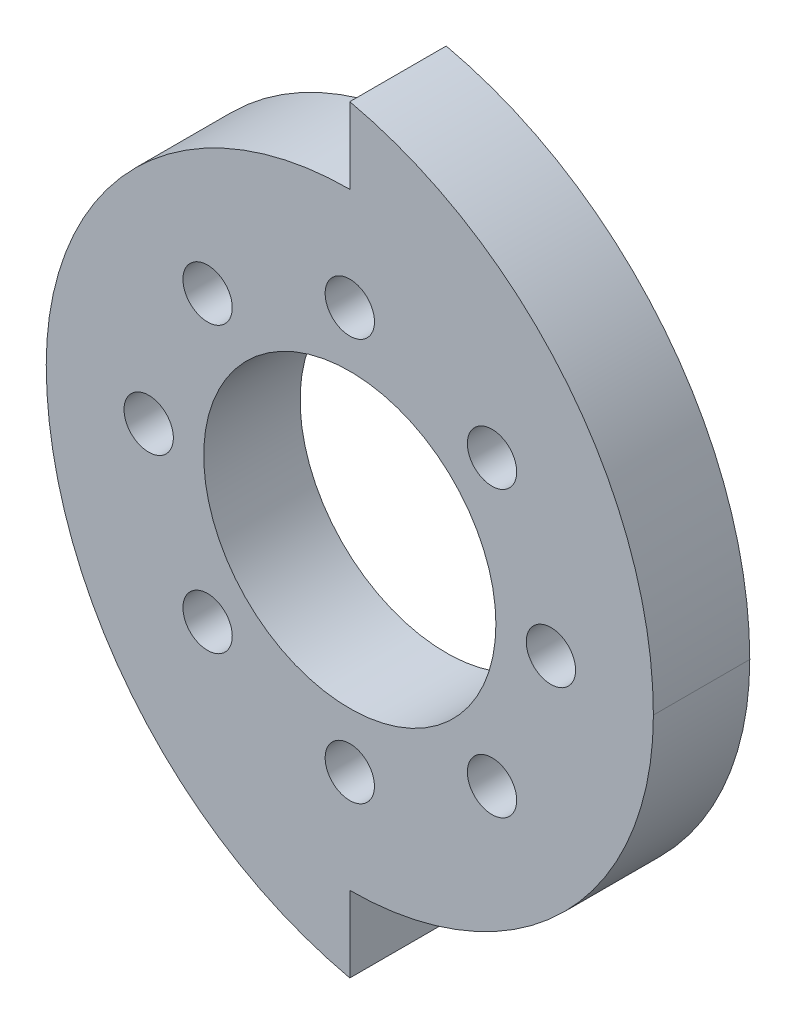
SolidWorks part; units mm, degrees
material "AISI 316 Stainless Steel Sheet (SS)"
ref_plane "Front Plane" through (0, 0, 0) normal (0, 0, 1) x (1, 0, 0)
ref_plane "Top Plane" through (0, 0, 0) normal (0, 1, 0) x (1, 0, 0)
ref_plane "Right Plane" through (0, 0, 0) normal (1, 0, 0) x (0, 0, -1)
sketch "Sketch3" plane through (0, 0, 0) normal (0, 0, 1) x (1, 0, 0)
  line L5 (0, 20) -> (0, 25)
  line L12 (0, -20) -> (0, -25)
  arc A9 (0, 25) -> (-20, 0) centre (5.625, 0) ccw construction
  arc A11 (0, -25) -> (20, 0) centre (-5.625, 0) ccw construction
  arc A14 (0, 25) -> (20, 0) centre (-5.625, 0) cw
  arc A15 (0, -25) -> (-20, 0) centre (5.625, 0) cw
  arc A16 (0, 20) -> (-20, 0) centre (0, 0) ccw
  arc A17 (20, 0) -> (0, -20) centre (0, 0) cw
  dimension "D2" = 5
  dimension "D1" = 40
extrude "Boss-Extrude1" add sketch "Sketch3" along normal blind 6.35
sketch "Sketch4" plane through (0, 0, 6.35) normal (0, 0, 1) x (1, 0, 0)
  line L0 (0, 11.625) -> (0, 9.625) construction
  circle A10 centre (0, 0) radius 9.625
  circle A11 centre (0, 13.25) radius 1.625
  point P5 (0, 9.625)
  dimension "D2" = 2
  dimension "D3" = 19.25
  dimension "D1" = 3.25
extrude "Cut-Extrude1" cut sketch "Sketch4" against normal through all
ref_axis "Axis1" through (0, 0, -0.475) along (0, 0, 1)
pattern_circular "CirPattern1" count 8 over 360 about axis through (0, 0, -0.475) along (0, 0, 1) of "Cut-Extrude1"
